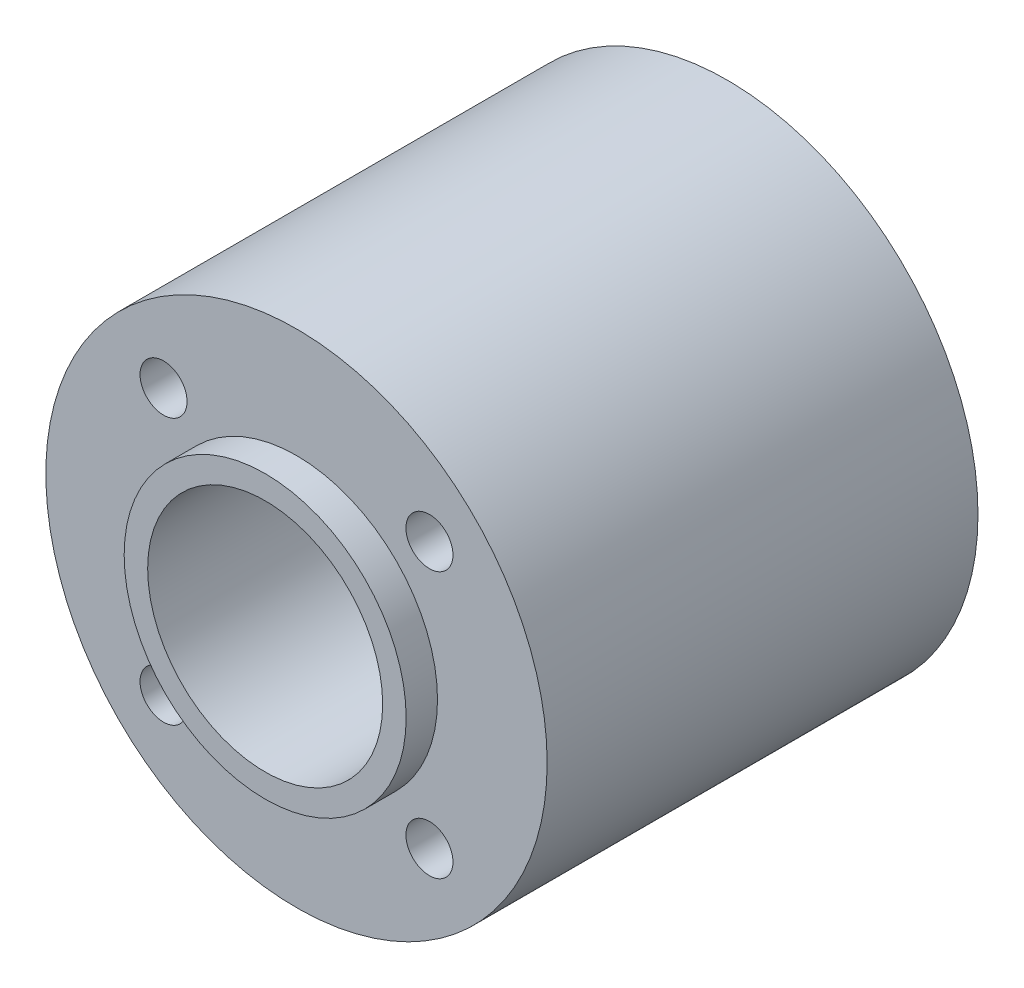
SolidWorks part; units mm, degrees
ref_plane "Plan de face" through (0, 0, 0) normal (0, 0, 1) x (1, 0, 0)
ref_plane "Plan de dessus" through (0, 0, 0) normal (0, 1, 0) x (1, 0, 0)
ref_plane "Plan de droite" through (0, 0, 0) normal (1, 0, 0) x (0, 0, -1)
sketch "Esquisse1" plane through (0, 0, 0) normal (0, 0, 1) x (1, 0, 0)
  circle A0 centre (0, 0) radius 16
  circle A1 centre (0, 0) radius 7.5
  circle A2 centre (0, 0) radius 9
  dimension "D1" = 32
  dimension "D2" = 15
  dimension "D3" = 18
extrude "Boss.-Extru.2" add sketch "Esquisse1" along normal blind 27.5 contours A2 A1 | A0 A2 region at (-15.5475, 0, 0) region at (-8.7454, 0, 0)
extrude "Boss.-Extru.3" add sketch "Esquisse1<5>" against normal blind 2 contours A2 A1 region at (-8.7454, 0, 0)
sketch "Esquisse1<5>" plane through (0, 0, 0) normal (0, 0, 1) x (1, 0, 0) same geometry as "Esquisse1"
extrude "Boss.-Extru.4" add sketch "Esquisse1<7>" along normal blind 2 from surface contours A2 A1 region at (-8.7454, 0, 0) starting at face at (7.5, 0, 27.5)
sketch "Esquisse1<7>" plane through (0, 0, 0) normal (0, 0, 1) x (1, 0, 0) same geometry as "Esquisse1"
sketch "Esquisse2" plane through (0, 0, 0) normal (0, 0, -1) x (-1, 0, 0)
  line L0 (0, 0) -> (0, 12) construction
  line L1 (0, 0) -> (-8.4853, 8.4853) construction
  circle A0 centre (0, 0) radius 12 construction
  circle A1 centre (-8.4853, 8.4853) radius 1.5
  circle A2 centre (8.4853, 8.4853) radius 1.5
  circle A3 centre (8.4853, -8.4853) radius 1.5
  circle A4 centre (-8.4853, -8.4853) radius 1.5
  circle A5 centre (0, 0) radius 9 construction
  dimension "D1" = 24
  dimension "D3" = 3
  dimension "D2" = 45
  dimension "D4" = 4
extrude "Enlèv. mat.-Extru.1" cut sketch "Esquisse2" against normal through all
